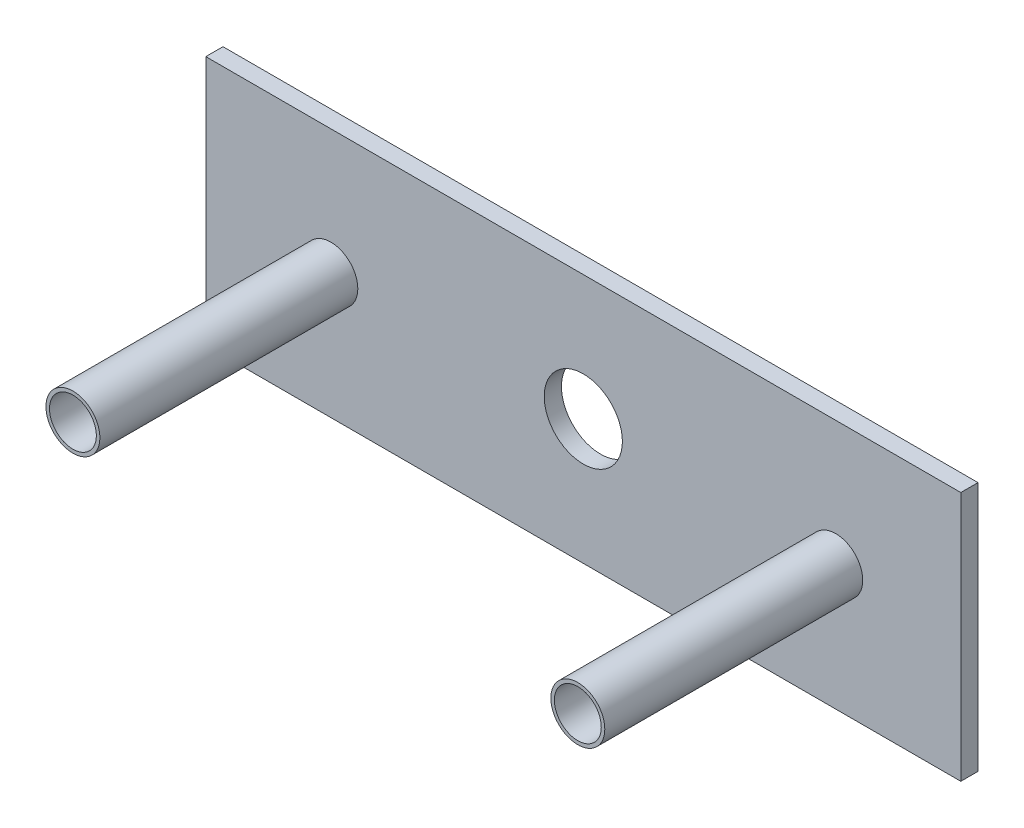
SolidWorks part; units mm, degrees
ref_plane "Plan de face" through (0, 0, 0) normal (0, 0, 1) x (1, 0, 0)
ref_plane "Plan de dessus" through (0, 0, 0) normal (0, 1, 0) x (1, 0, 0)
ref_plane "Plan de droite" through (0, 0, 0) normal (1, 0, 0) x (0, 0, -1)
sketch "Esquisse1" plane through (0, 0, 0) normal (0, 0, 1) x (1, 0, 0)
  line L1 (-47.6288, 18.2599) -> (48.9712, 18.2599)
  line L2 (-47.6288, 18.2599) -> (-47.6288, -13.7401)
  line L3 (-47.6288, -13.7401) -> (48.9712, -13.7401)
  line L4 (48.9712, 18.2599) -> (48.9712, -13.7401)
  dimension "D1" = 96.6
  dimension "D2" = 32
extrude "Boss.-Extru.1" add sketch "Esquisse1" along normal blind 2.2
sketch "Esquisse6" plane through (0, 0, 2.2) normal (0, 0, 1) x (1, 0, 0)
  line L0 (-47.6288, 18.2599) -> (-47.6288, -13.7401) construction
  line L3 (48.9712, 18.2599) -> (-47.6288, 18.2599) construction
  line L4 (48.9712, -13.7401) -> (48.9712, 18.2599) construction
  circle A0 centre (-31.6288, 2.2599) radius 3.45
  circle A1 centre (32.9712, 2.2599) radius 3.45
  dimension "D1" = 6.9
  dimension "D4" = 6.9
  dimension "D2" = 16
  dimension "D3" = 16
  dimension "D5" = 16
  dimension "D6" = 16
extrude "Boss.-Extru.2" add sketch "Esquisse6" along normal blind 33
sketch "Esquisse7" plane through (0, 0, 35.2) normal (0, 0, 1) x (1, 0, 0)
  line L1 (-47.6288, 18.2599) -> (-47.6288, -13.7401) construction
  line L3 (48.9712, 18.2599) -> (-47.6288, 18.2599) construction
  line L4 (48.9712, -13.7401) -> (48.9712, 18.2599) construction
  line L5 (-47.6288, -13.7401) -> (48.9712, -13.7401) construction
  circle A0 centre (-31.6288, 2.2599) radius 3
  circle A1 centre (32.9712, 2.2599) radius 3
  circle A2 centre (0.6712, 2.2599) radius 5
  dimension "D1" = 6
  dimension "D4" = 6
  dimension "D7" = 10
  dimension "D2" = 16
  dimension "D3" = 16
  dimension "D5" = 16
  dimension "D6" = 16
  dimension "D8" = 16
  dimension "D9" = 48.3
extrude "Enlèv. mat.-Extru.1" cut sketch "Esquisse7" against normal through all
